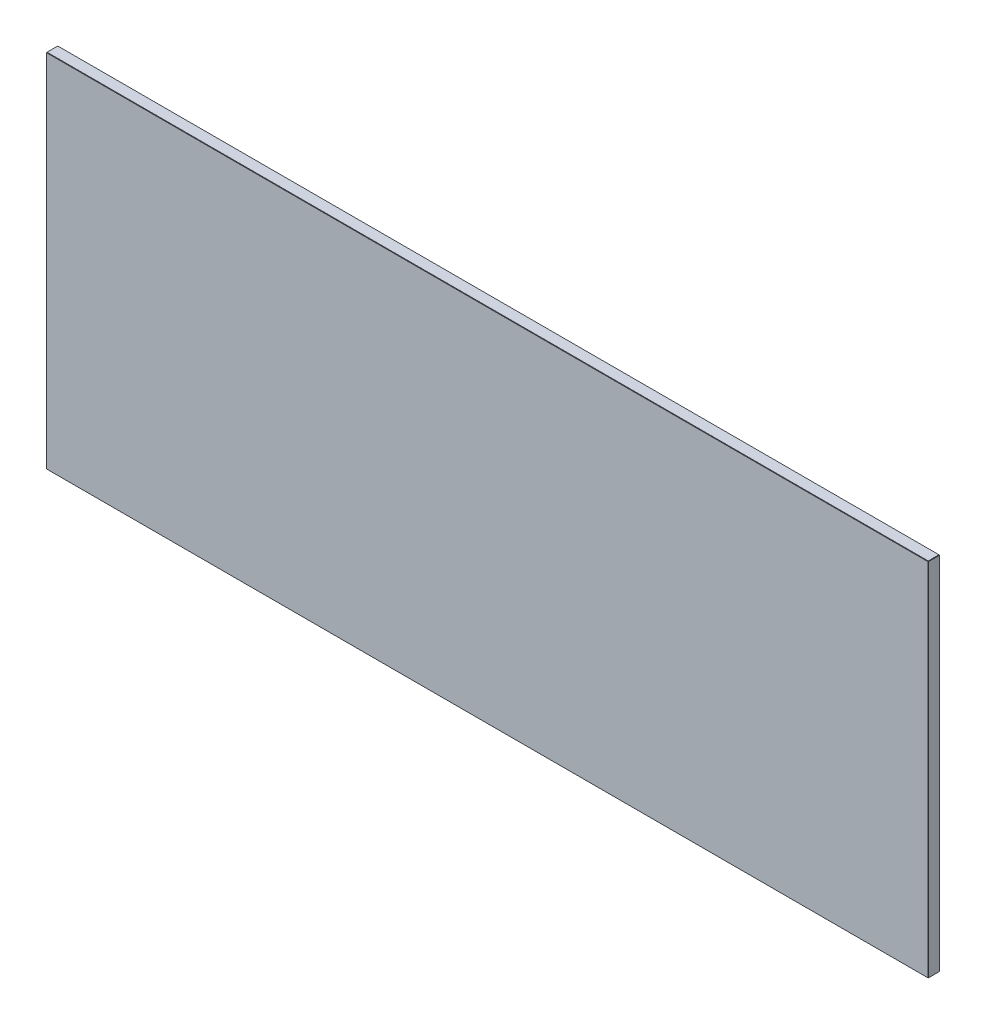
SolidWorks part; units mm, degrees
material "A5052P-H112"
ref_plane "Front Plane" through (0, 0, 0) normal (0, 0, 1) x (1, 0, 0)
ref_plane "Top Plane" through (0, 0, 0) normal (0, 1, 0) x (1, 0, 0)
ref_plane "Right Plane" through (0, 0, 0) normal (1, 0, 0) x (0, 0, -1)
sketch "Sketch1" plane through (15.083, 7.2287, 0) normal (0, 0, 1) x (1, 0, 0)
  line L1 (-707.5, -290) -> (25, -290)
  line L2 (-707.5, -290) -> (-707.5, 10)
  line L3 (-707.5, 10) -> (25, 10)
  line L4 (25, -290) -> (25, 10)
  dimension "A" = 732.5
  dimension "B" = 300
extrude "Boss-Extrude1" add sketch "Sketch1" along normal blind 9.5
chamfer "Chamfer1" distance 0.3 angle 45 12 edges at (40.083, -282.7713, 4.75) (-326.167, -282.7713, 0) (-326.167, -282.7713, 9.5) (-692.417, -282.7713, 4.75) (-692.417, -132.7713, 0) (-692.417, -132.7713, 9.5) (40.083, -132.7713, 9.5) (40.083, -132.7713, 0) (-326.167, 17.2287, 0) (40.083, 17.2287, 4.75) (-692.417, 17.2287, 4.75) (-326.167, 17.2287, 9.5)
other "DeleteFace1" [suppressed]
chamfer "Chamfer2" [suppressed] distance 1 angle 45
other "DeleteFace2" [suppressed]
chamfer "Chamfer3" [suppressed] distance 1 angle 45
other "DeleteFace3" [suppressed]
chamfer "Chamfer4" [suppressed] distance 1 angle 45
other "DeleteFace4" [suppressed]
chamfer "Chamfer5" [suppressed] distance 1 angle 45
